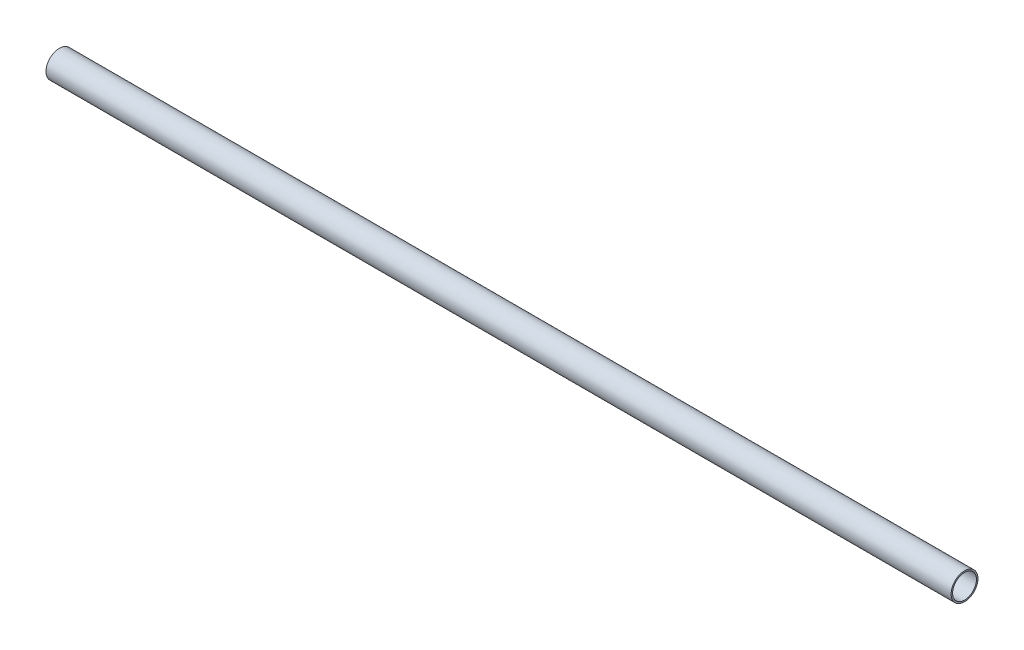
SolidWorks part; units mm, degrees
material "Brass"
ref_plane "Front" through (0, 0, 0) normal (0, 0, 1) x (1, 0, 0)
ref_plane "Top" through (0, 0, 0) normal (0, 1, 0) x (1, 0, 0)
ref_plane "Right" through (0, 0, 0) normal (1, 0, 0) x (0, 0, -1)
ref_axis "side-side" through (80.9, 0, 0) along (-1, 0, 0)
ref_axis "up-down" through (0, 50, 0) along (0, -1, 0)
ref_axis "front-back" through (0, 0, -80.9) along (0, 0, 1)
sketch "Sketch1" plane through (0, 0, 0) normal (1, 0, 0) x (0, 0, -1)
  circle A0 centre (0, 0) radius 3.175
  dimension "D1" = 6.35
extrude "Extrude-Thin1" add sketch "Sketch1" along normal blind 82.55 and the other way blind 131.0386 thin thin type one direction reverse wall 0.3556
